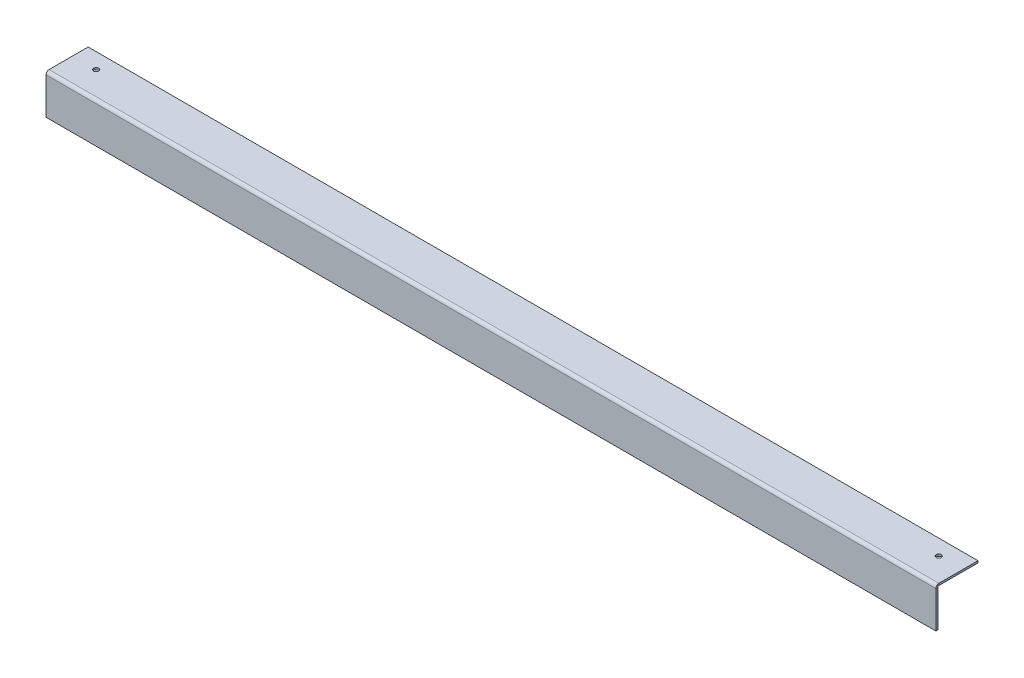
SolidWorks part; units mm, degrees
note: The reader was unsure of these and kept them because the rebuilt part matched: flange length of "Edge-Flange1".
ref_plane "Front Plane" through (0, 0, 0) normal (0, 0, 1) x (1, 0, 0)
ref_plane "Top Plane" through (0, 0, 0) normal (0, 1, 0) x (1, 0, 0)
ref_plane "Right Plane" through (0, 0, 0) normal (1, 0, 0) x (0, 0, -1)
sketch "Sketch1" plane through (0, 0, 0) normal (0, 1, 0) x (1, 0, 0)
  line L1 (-596.9, 26.9875) -> (596.9, 26.9875)
  line L2 (-596.9, 26.9875) -> (-596.9, -26.9875)
  line L3 (-596.9, -26.9875) -> (596.9, -26.9875)
  line L4 (596.9, 26.9875) -> (596.9, -26.9875)
  line L5 (-596.9, 26.9875) -> (596.9, -26.9875) construction
  line L6 (-596.9, -26.9875) -> (596.9, 26.9875) construction
  point P0 (0, 0)
  dimension "D1" = 1193.8
  dimension "D2" = 53.975
base flange "Base-Flange1" sketch "Sketch1" thickness 2.5883 reverse thickness direction no parameters "D1"=1.524
edge flange "Edge-Flange1" sketch "Sketch8" flange angle 90 flange length 50.8 flange position material outside bend radius 1.524 thickness 2.5883 relief rectangular parameters "D1"=1.5, "D6"=10
sketch "Sketch8" plane through (0, -2.5883, 26.9875) normal (0, 0, -1) x (1, 0, 0)
  line L2 (-596.9, 0) -> (-596.9, 50.8)
  line L3 (-596.9, 50.8) -> (596.9, 50.8)
  line L4 (596.9, 50.8) -> (596.9, 0)
  line L5 (596.9, 0) -> (-596.9, 0) construction
  line L6 (596.9, 0) -> (-596.9, 0)
bend "EdgeBend1" bend radius 1.524 bend angle 90 parameters "D5"=1
hole_wizard "1/4 Clearance Hole1" positions "Sketch9" profile "Sketch10" hole size "1/4" standard "ANSI Inch" end condition through all
sketch "Sketch9" plane through (0, 0, 0) normal (0, 1, 0) x (1, 0, 0)
  line L0 (0, -25.4635) -> (0, 26.9875) construction
  line L1 (-596.9, -25.4635) -> (596.9, -25.4635) construction
  line L2 (596.9, 26.9875) -> (-596.9, 26.9875) construction
  line L4 (-622.3, 6.0325) -> (622.3, 6.0325) construction
  line L6 (596.9, -25.4635) -> (596.9, 26.9875) construction
  point P0 (565.15, 6.0325)
  point P2 (-565.15, 6.0325)
  dimension "D1" = 31.75
  dimension "D2" = 20.955
sketch "Sketch10" plane through (565.15, 0, -6.0325) normal (1, 0, 0) x (0, 0, 1)
  line L0 (0, 0) -> (0, 53.3883)
  line L1 (0, 53.3883) -> (3.3782, 53.3883)
  line L2 (3.3782, 53.3883) -> (3.3782, 0)
  line L5 (3.3782, 0) -> (0, 0)
  line L11 (0, -6.35) -> (0, 107.95) construction
  dimension "Thru Hole Dia." = 6.7564
  dimension "Thru Hole Depth" = 53.3883
sketch "Bend-Lines1" [suppressed] plane through (0, 0, 0) normal (0, 1, 0) x (1, 0, 0)
sketch "Bounding-Box1" [suppressed] plane through (0, 0, 0) normal (0, 1, 0) x (1, 0, 0)
sheet metal parameters "Sheet-Metal1" thickness 2.5883 parameters "D1"=1.5
flat pattern "Flat-Pattern1" [suppressed]
sketch "Bend-Lines2" plane through (0, 0, 0) normal (0, 1, 0) x (1, 0, 0)
sketch3d "Bounding-Box2" [suppressed]
  line L0 (-609.6, -25.4, 0) -> (609.6, -25.4, 0) construction
  line L1 (-609.6, 25.4, 0) -> (609.6, 25.4, 0) construction
  line L2 (-609.6, -25.4, 0) -> (-609.6, 25.4, 0) construction
  line L3 (609.6, -25.4, 0) -> (609.6, 25.4, 0) construction
sheet metal parameters "Sheet-Metal2" thickness 2.5883 parameters "D1"=1.5
flat pattern "Flat-Pattern1"
sketch "Bend-Lines2" plane through (0, 0, 0) normal (0, 1, 0) x (1, 0, 0)
  line L0 (-609.6, -25.6671) -> (609.6, -25.6671) construction
  line L1 (-609.6, -25.6671) -> (609.6, -25.6671) construction
sketch3d "Bounding-Box2" [suppressed]
  line L0 (609.6, -76.7343, 0) -> (-609.6, -76.7343, 0) construction
  line L1 (609.6, 25.4, 0) -> (-609.6, 25.4, 0) construction
  line L2 (609.6, -76.7343, 0) -> (609.6, 25.4, 0) construction
  line L3 (-609.6, -76.7343, 0) -> (-609.6, 25.4, 0) construction
bend of the flat pattern "Flatten-<EdgeBend1>1"
sheet metal parameters "Sheet-Metal3" thickness 2.5883 parameters "D1"=1.5
flat pattern "Flat-Pattern1"
sketch "Bend-Lines2" plane through (0, 0, 0) normal (0, 1, 0) x (1, 0, 0)
  line L0 (-596.9, -27.4168) -> (596.9, -27.4168) construction
  line L1 (-596.9, -27.4168) -> (596.9, -27.4168) construction
sketch3d "Bounding-Box2" [suppressed]
  line L0 (596.9, -78.646, 0) -> (-596.9, -78.646, 0) construction
  line L1 (596.9, 26.9875, 0) -> (-596.9, 26.9875, 0) construction
  line L2 (596.9, -78.646, 0) -> (596.9, 26.9875, 0) construction
  line L3 (-596.9, -78.646, 0) -> (-596.9, 26.9875, 0) construction
bend of the flat pattern "Flatten-<EdgeBend1>1"
